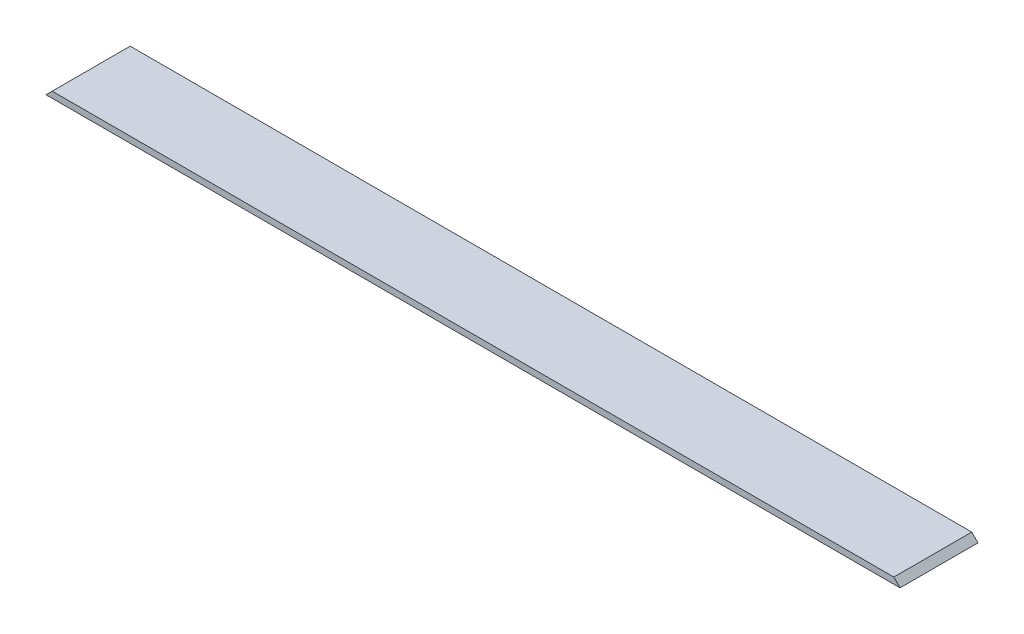
SolidWorks part; units mm, degrees
material "Pine"
ref_plane "Front Plane" through (0, 0, 0) normal (0, 0, 1) x (1, 0, 0)
ref_plane "Top Plane" through (0, 0, 0) normal (0, 1, 0) x (1, 0, 0)
ref_plane "Right Plane" through (0, 0, 0) normal (1, 0, 0) x (0, 0, -1)
sketch "Sketch1" plane through (0, 0, 0) normal (0, 0, 1) x (1, 0, 0)
  line L0 (-246.2013, 0) -> (449.7587, 0)
  line L1 (449.7587, 0) -> (444.6787, 5.08)
  line L2 (444.6787, 5.08) -> (-241.1213, 5.08)
  line L3 (-241.1213, 5.08) -> (-246.2013, 0)
  point P5 (638.6518, 0)
  point P6 (625.1776, 0)
  point P7 (444.6787, 5.08)
  dimension "D1" = 5.08
  dimension "D2" = 685.8
  dimension "D3" = 45
  dimension "D4" = 45
extrude "Boss-Extrude1" add sketch "Sketch1" along normal blind 63.5
